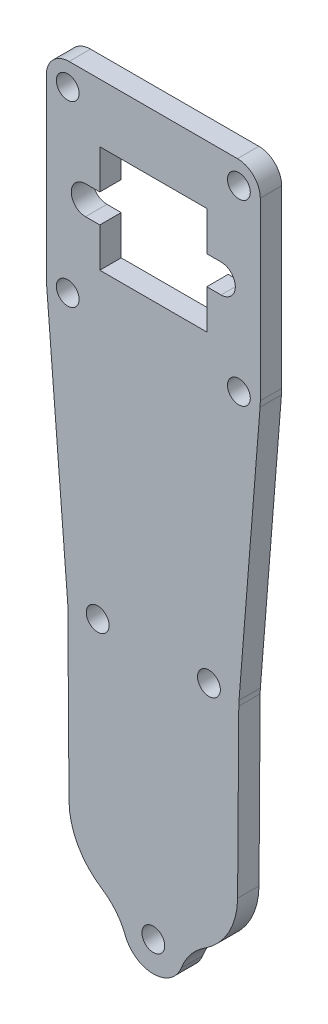
SolidWorks part; units mm, degrees
ref_plane "Front Plane" through (0, 0, 0) normal (0, 0, 1) x (1, 0, 0)
ref_plane "Top Plane" through (0, 0, 0) normal (0, 1, 0) x (1, 0, 0)
ref_plane "Right Plane" through (0, 0, 0) normal (1, 0, 0) x (0, 0, -1)
sketch "Sketch1" plane through (0, 0, 0) normal (0, 0, 1) x (1, 0, 0)
  line L0 (-7.8, 0) -> (7.8, 0) construction
  line L1 (7.8, 0) -> (0, -35) construction
  line L2 (0, -35) -> (-7.8, 0) construction
  line L3 (-11.9867, -0.3335) -> (-11.77, -31.11)
  line L4 (11.9867, -0.3335) -> (11.77, -31.11)
  line L5 (0, 62.5) -> (0, 37.5) construction
  line L6 (-15, 62.5) -> (15, 62.5) construction
  line L7 (-15, 62.5) -> (-15, 37.5) construction
  line L8 (-15, 37.5) -> (15, 37.5) construction
  line L9 (15, 62.5) -> (15, 37.5) construction
  line L10 (-11.9867, -0.3335) -> (-15, 37.5)
  line L11 (11.9867, -0.3335) -> (15, 37.5)
  line L12 (-15, 37.5) -> (-15, 62.5)
  line L13 (-11.8, 65.7) -> (11.8, 65.7)
  line L14 (15, 62.5) -> (15, 37.5)
  line L15 (-11.77, -31.11) -> (-1.5836, -31.11) construction
  line L16 (1.5836, -31.11) -> (11.77, -31.11) construction
  line L17 (-11.5, 50) -> (11.5, 50) construction
  line L18 (-7.5, 57.5) -> (7.5, 57.5)
  line L19 (-7.5, 57.5) -> (-7.5, 42.5)
  line L20 (-7.5, 42.5) -> (7.5, 42.5)
  line L21 (7.5, 57.5) -> (7.5, 42.5)
  line L22 (-7.5, 52) -> (-11.5, 52)
  line L23 (-7.5, 52) -> (-7.5, 48)
  line L24 (-7.5, 48) -> (-11.5, 48)
  line L25 (-11.5, 52) -> (-11.5, 48)
  line L26 (7.5, 52) -> (11.5, 52)
  line L27 (7.5, 52) -> (7.5, 48)
  line L28 (7.5, 48) -> (11.5, 48)
  line L29 (11.5, 52) -> (11.5, 48)
  circle A0 centre (0, -35) radius 1.6
  circle A1 centre (-7.8, 0) radius 1.6
  circle A2 centre (7.8, 0) radius 1.6
  circle A3 centre (-7.8, 0) radius 4.2
  circle A4 centre (7.8, 0) radius 4.2
  circle A5 centre (0, -35) radius 4.2
  circle A6 centre (-12, 62.5) radius 1.6
  circle A7 centre (12, 62.5) radius 1.6
  circle A8 centre (12, 37.5) radius 1.6
  circle A9 centre (-12, 37.5) radius 1.6
  circle A10 centre (0, 50) radius 7.5 construction
  arc A11 (11.8, 65.7) -> (15, 62.5) centre (11.8, 62.5) cw
  arc A12 (-15, 62.5) -> (-11.8, 65.7) centre (-11.8, 62.5) cw
  arc A13 (-3.9212, -36.5048) -> (-11.77, -31.11) centre (-11.77, -39.517) ccw
  arc A14 (3.9212, -36.5048) -> (11.77, -31.11) centre (11.77, -39.517) cw
  point P7 (0, 0)
  dimension "D3" = 3.2
  dimension "D4" = 8.4
  dimension "D9" = 15
  dimension "D10" = 3.2
  dimension "D1" = 15.6
  dimension "D2" = 35
  dimension "D5" = 30
  dimension "D6" = 25
  dimension "D7" = 24
  dimension "D8" = 12
  dimension "D11" = 11.77
  dimension "D12" = 11.77
  dimension "D13" = 3.89
  dimension "D14" = 50
  dimension "D15" = 15
  dimension "D16" = 4
  dimension "D17" = 4
  dimension "D18" = 4
extrude "Boss-Extrude1" add sketch "Sketch1" along normal blind 3 contours A12 L12 L10 A3 A5 A4 L11 L14 A11 L13 A10 A9 A8 A7 A6 | A3 A1 | A4 A2 | A5 A0 region at (3.722, 0.1621, 0) region at (0, 16.3651, 0) region at (-7.9621, 4.078, 0) region at (-0.7436, -30.9871, 0)
fillet "Fillet1" radius 10 6 edges at (-11.9867, -0.3335, 1.5) (-15, 37.5, 1.5) (11.9867, -0.3335, 1.5) (15, 37.5, 1.5) (11.77, -31.11, 1.5) (-11.77, -31.11, 1.5)
fillet "Fillet2" 2 edges at (-11.5, 48, 1.5) (-11.5, 52, 1.5) type full round first side face at (-9.5, 48, 1.5) second side face at (-9.5, 52, 1.5) middle face at (-11.5, 50, 1.5)
fillet "Fillet3" 2 edges at (11.5, 48, 1.5) (11.5, 52, 1.5) type full round first side face at (9.5, 48, 1.5) second side face at (9.5, 52, 1.5) middle face at (11.5, 50, 1.5)
